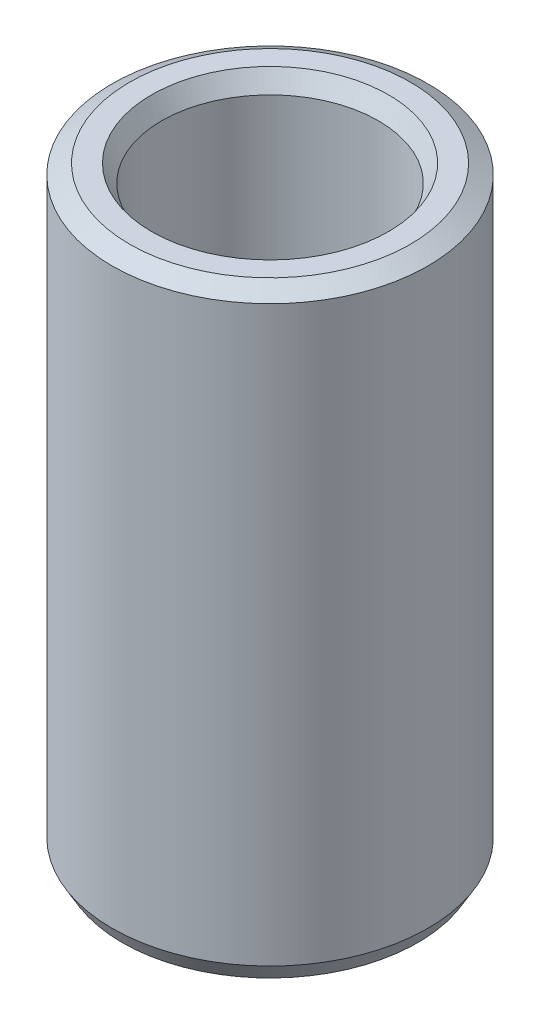
SolidWorks part; units mm, degrees
ref_plane "Front Plane" through (0, 0, 0) normal (0, 0, 1) x (1, 0, 0)
ref_plane "Top Plane" through (0, 0, 0) normal (0, 1, 0) x (1, 0, 0)
ref_plane "Right Plane" through (0, 0, 0) normal (1, 0, 0) x (0, 0, -1)
sketch "Sketch1" plane through (0, 0, 0) normal (0, 1, 0) x (1, 0, 0)
  circle A0 centre (0, 0) radius 50
  dimension "SLEEVE_OD" = 100
extrude "Boss-Extrude1" add sketch "Sketch1" along normal blind 190.3858
sketch "Sketch2" plane through (0, 0, 0) normal (0, 1, 0) x (1, 0, 0)
  circle A0 centre (0, 0) radius 34.3377
  dimension "BORE_D" = 68.6754
extrude "Cut-Extrude1" cut sketch "Sketch2" along normal through all
chamfer "Chamfer1" distance 3.1946 angle 60 4 edges at (0, 190.3858, 34.3377) (0, 0, 34.3377) (0, 0, 50) (0, 190.3858, 50) first distance on face at (0, 190.3858, 34.3377) first distance on face at (0, 0, 34.3377) first distance on face at (0, 190.3858, 50)
